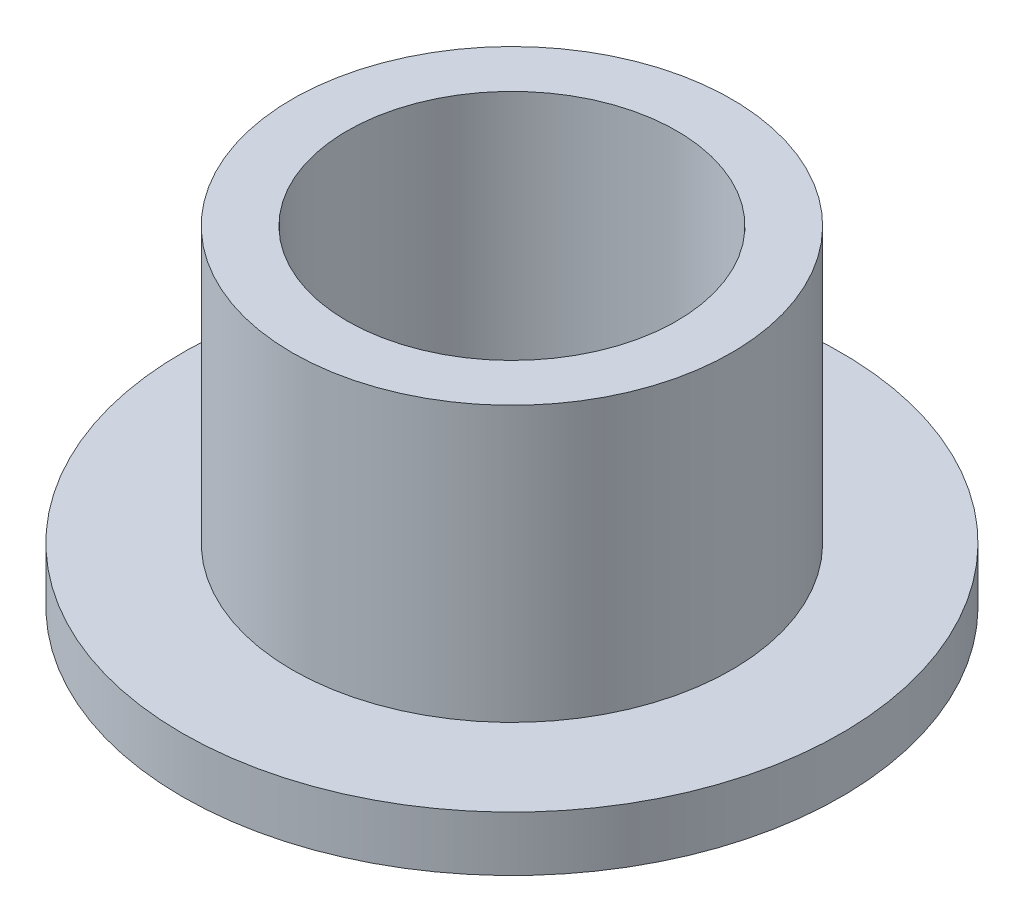
SolidWorks part; units mm, degrees
material "Polyethylene Cross-Linked"
ref_plane "Front" through (0, 0, 0) normal (0, 0, 1) x (1, 0, 0)
ref_plane "Top" through (0, 0, 0) normal (0, 1, 0) x (1, 0, 0)
ref_plane "Right" through (0, 0, 0) normal (1, 0, 0) x (0, 0, -1)
sketch "Sketch1" plane through (0, 0, 0) normal (0, 1, 0) x (1, 0, 0)
  line L0 (0, 3) -> (0, 4) construction
  circle A0 centre (0, 0) radius 3
  circle A1 centre (0, 0) radius 4
  circle A2 centre (0, 0) radius 6
  point P7 (0, 3.3333)
  dimension "ID" = 6
  dimension "OD" = 8
  dimension "FlangeOD" = 12
  dimension "D1" = 1
  dimension "D2" = 0.3333
sketch "Sketch2" plane through (0, 0, 0) normal (0, 1, 0) x (1, 0, 0)
  circle A0 centre (0, 0) radius 3 construction
  circle A1 centre (0, 0) radius 4 construction
  circle A2 centre (0, 0) radius 3
  circle A3 centre (0, 0) radius 4
extrude "Boss-Extrude1" add sketch "Sketch2" along normal blind 6
sketch "Sketch3" plane through (0, 0, 0) normal (0, 1, 0) x (1, 0, 0)
  circle A0 centre (0, 0) radius 6 construction
  circle A1 centre (0, 0) radius 4 construction
  circle A2 centre (0, 0) radius 6
  circle A3 centre (0, 0) radius 4
extrude "Boss-Extrude2" add sketch "Sketch3" along normal blind 1
sketch "Sketch4" plane through (0, 0, 0) normal (1, 0, 0) x (0, 0, -1)
  line L0 (0, 0) -> (0, 6) construction
  line L1 (6, 0) -> (6, 1) construction
  line L3 (3.1524, 6) -> (3.0762, 6)
  line L4 (3.0762, 0.0762) -> (3.0762, 6)
  line L5 (3.0762, 0.0762) -> (6, 0.0762)
  line L6 (6, 0.0762) -> (6, 0.1524)
  line L7 (6, 0.1524) -> (3.1524, 0.1524)
  line L8 (3.1524, 0.1524) -> (3.1524, 6)
  line L9 (-6, 0) -> (6, 0) construction
  line L10 (4, 6) -> (-4, 6) construction
  line L12 (3, 6) -> (3, 0) construction
  line L13 (3, 6) -> (-3, 6) construction
  dimension "D1" = 0.0762
  dimension "D2" = 0.0762
  dimension "D3" = 0.0762
ref_plane "Contact Plane 1" through (0, 6, 0) normal (0, 1, 0) x (1, 0, 0)
ref_plane "Contact Plane 2" through (0, 0, 0) normal (0, -1, 0) x (-1, 0, 0)
ref_axis "Center Axis 1" through (0, 6, 0) along (0, -1, 0)
equation "\"D2@Sketch1\" = \"D1@Sketch1\"/3"
